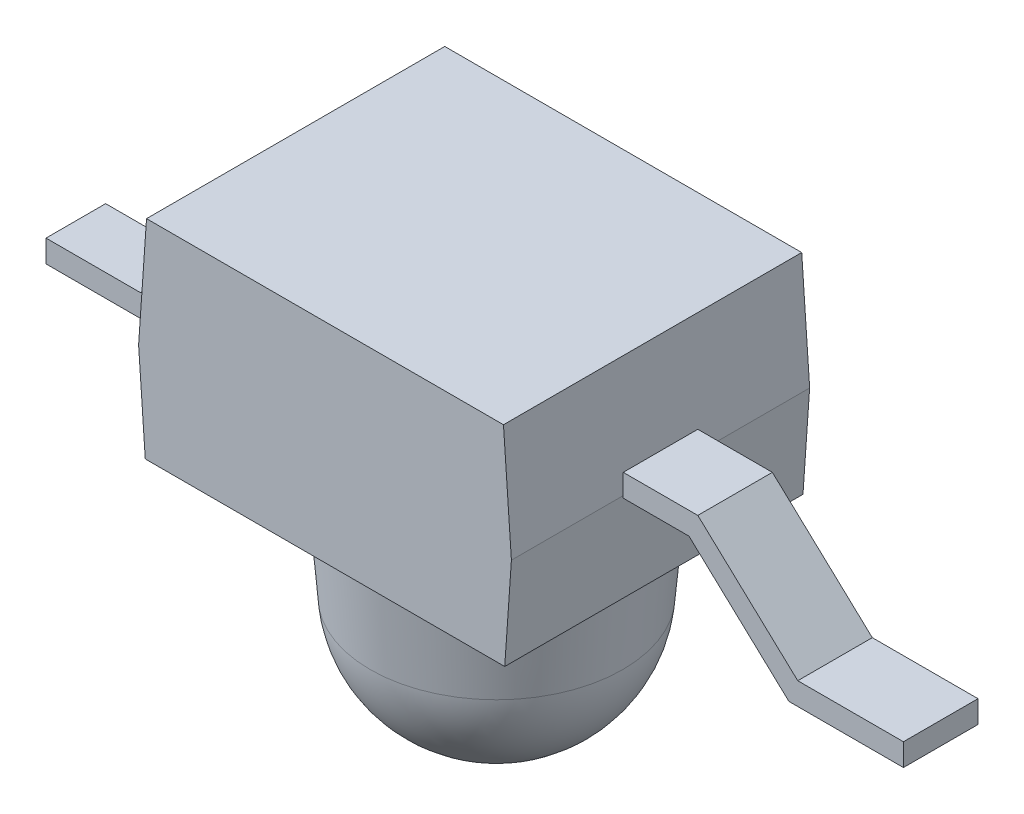
SolidWorks part; units mm, degrees
note: The reader was unsure of these and kept them because the rebuilt part matched: shared geometry of "Sketch1<3>", "Sketch1<5>", "Sketch1<6>".
ref_plane "Front Plane" through (0, 0, 0) normal (0, 0, 1) x (1, 0, 0)
ref_plane "Top Plane" through (0, 0, 0) normal (0, 1, 0) x (1, 0, 0)
ref_plane "Right Plane" through (0, 0, 0) normal (1, 0, 0) x (0, 0, -1)
sketch "Sketch1" plane through (0, 0, 0) normal (0, 0, 1) x (1, 0, 0)
  line L0 (-1.25, 0.7) -> (1.25, -0.7) construction
  line L1 (-1.25, 0.7) -> (1.25, 0.7)
  line L2 (-1.25, 0.7) -> (-1.25, -0.7)
  line L3 (-1.25, -0.7) -> (1.25, -0.7)
  line L4 (1.25, 0.7) -> (1.25, -0.7)
  line L5 (1.1969, 0) -> (1.75, 0) construction
  line L6 (1.1969, 0.075) -> (1.75, 0.075)
  line L7 (1.1969, 0.075) -> (1.1969, -0.075)
  line L8 (-1.25, -0.06) -> (-1.1969, 0.7)
  line L9 (-1.25, -0.06) -> (-1.2052, -0.7)
  line L10 (0, 0) -> (0, -0.7) construction
  line L11 (1.25, -0.06) -> (1.1969, 0.7)
  line L12 (1.25, -0.06) -> (1.2052, -0.7)
  line L13 (1.1969, -0.075) -> (1.75, -0.075)
  line L14 (1.75, 0.075) -> (1.75, -0.075)
  line L15 (1.75, 0.075) -> (2.4202, -0.55)
  line L17 (2.4202, -0.55) -> (3.129, -0.55)
  line L18 (0.15, -0.7) -> (0.15, -2.1)
  line L19 (0.9969, -1.3222) -> (1.05, -0.7)
  line L20 (1.05, -0.7) -> (0.15, -0.7)
  line L21 (2.3611, -0.7) -> (3.129, -0.7)
  line L22 (1.6909, -0.075) -> (2.3611, -0.7)
  line L23 (3.129, -0.55) -> (3.129, -0.7)
  line L24 (-1.3669, 0.075) -> (-2.0371, -0.55)
  line L25 (-2.0371, -0.55) -> (-2.671, -0.55)
  line L26 (-1.978, -0.7) -> (-2.671, -0.7)
  line L27 (-1.3078, -0.075) -> (-1.978, -0.7)
  line L28 (-2.671, -0.55) -> (-2.671, -0.7)
  line L29 (-1.3669, 0.075) -> (-1.3669, -0.075)
  line L30 (-1.1969, -0.075) -> (-1.3669, -0.075)
  line L31 (-1.1969, 0.075) -> (-1.1969, -0.075)
  line L32 (-1.1969, 0.075) -> (-1.3669, 0.075)
  arc A1 (0.15, -2.1) -> (0.9969, -1.3222) centre (0.15, -1.25) ccw
  dimension "D3" = 0.15
  dimension "D15" = 0.85
  dimension "D1" = 2.5
  dimension "D2" = 2.8
  dimension "D4" = 0.15
  dimension "D5" = 0.5
  dimension "D6" = 137
  dimension "D7" = 0.76
  dimension "D8" = 4
  dimension "D9" = 4
  dimension "D10" = 0.17
  dimension "D11" = 0.15
  dimension "D12" = 0.15
  dimension "D13" = 1.4
  dimension "D14" = 0.9
  dimension "D16" = 1.1
  dimension "D17" = 137
  dimension "D18" = 5.8
  dimension "D19" = 0.6339
extrude "Extrude1" add sketch "Sketch1" along normal mid plane 2
extrude "Extrude2" add sketch "Sketch1<3>" along normal mid plane 0.5
sketch "Sketch1<3>" plane through (0, 0, 0) normal (0, 0, 1) x (1, 0, 0) same geometry as "Sketch1"
extrude "Extrude3" add sketch "Sketch1<5>" along normal mid plane 0.4
sketch "Sketch1<5>" plane through (0, 0, 0) normal (0, 0, 1) x (1, 0, 0) same geometry as "Sketch1"
revolve "Revolve1" add sketch "Sketch1<6>" angle 360 about L18
sketch "Sketch1<6>" plane through (0, 0, 0) normal (0, 0, 1) x (1, 0, 0) same geometry as "Sketch1"
